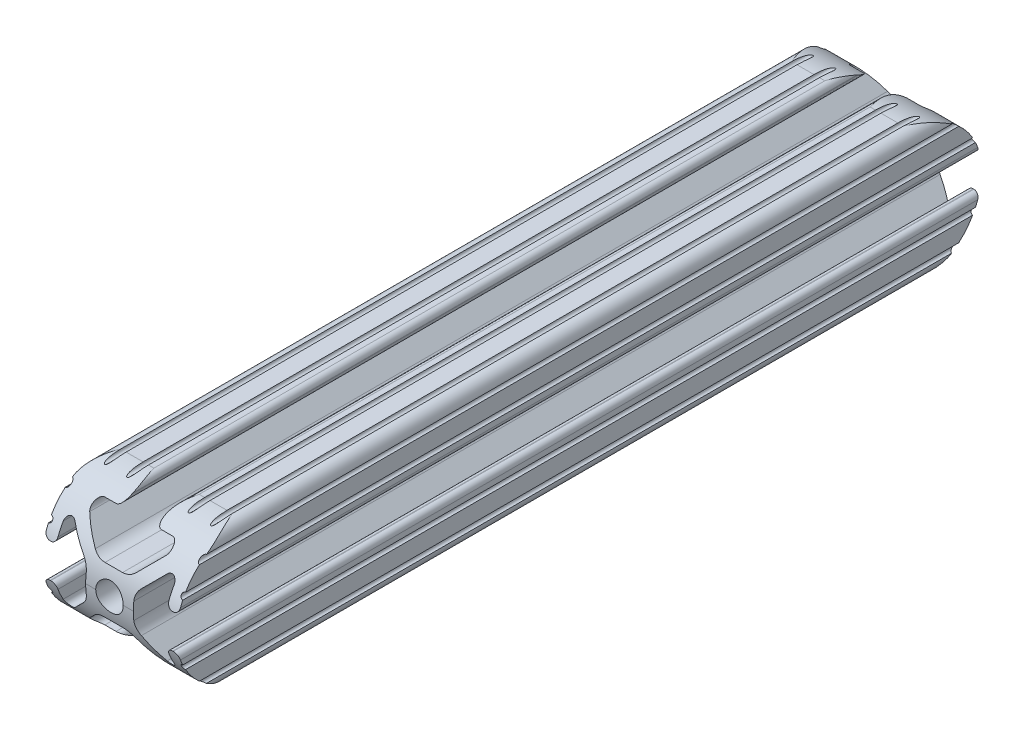
SolidWorks part; units mm, degrees
material "6061 Alloy"
ref_plane "Front Plane" through (0, 0, 0) normal (0, 0, 1) x (1, 0, 0)
ref_plane "Top Plane" through (0, 0, 0) normal (0, 1, 0) x (1, 0, 0)
ref_plane "Right Plane" through (0, 0, 0) normal (1, 0, 0) x (0, 0, -1)
sketch "Sketch1" plane through (0, 0, 0) normal (0, 0, 1) x (1, 0, 0)
  line L88 (-7.1797, -8.6452) -> (-3.9523, -5.4237)
  line L89 (-1.7093, -4.4958) -> (1.7093, -4.4958)
  line L90 (3.9523, -5.4237) -> (7.1797, -8.6452)
  line L91 (6.4164, -10.4902) -> (4.2875, -10.4902)
  line L92 (3.2385, -11.5392) -> (3.2385, -11.651)
  line L93 (4.2875, -12.7) -> (5.3171, -12.7)
  line L94 (6.3331, -12.7) -> (9.5504, -12.7)
  line L95 (12.7, -9.5504) -> (12.7, -6.3331)
  line L96 (12.7, -5.3171) -> (12.7, -4.2875)
  line L97 (11.651, -3.2385) -> (11.5392, -3.2385)
  line L98 (10.4902, -4.2875) -> (10.4902, -6.4021)
  line L99 (8.7371, -7.1294) -> (5.441, -3.8408)
  line L100 (4.5085, -1.5932) -> (4.5085, 1.5932)
  line L101 (5.441, 3.8408) -> (8.7371, 7.1294)
  line L102 (10.4902, 6.4021) -> (10.4902, 4.2875)
  line L103 (11.5392, 3.2385) -> (11.651, 3.2385)
  line L104 (12.7, 4.2875) -> (12.7, 5.3171)
  line L105 (12.7, 6.3331) -> (12.7, 9.5504)
  line L106 (9.5504, 12.7) -> (6.3331, 12.7)
  line L107 (5.3171, 12.7) -> (4.2875, 12.7)
  line L108 (3.2385, 11.651) -> (3.2385, 11.5392)
  line L109 (4.2875, 10.4902) -> (6.4768, 10.4902)
  line L110 (7.207, 8.7244) -> (3.8983, 5.4232)
  line L111 (1.6558, 4.4958) -> (-1.6558, 4.4958)
  line L112 (-3.8983, 5.4232) -> (-7.207, 8.7244)
  line L113 (-6.4768, 10.4902) -> (-4.2875, 10.4902)
  line L114 (-3.2385, 11.5392) -> (-3.2385, 11.651)
  line L115 (-4.2875, 12.7) -> (-5.3171, 12.7)
  line L116 (-6.3331, 12.7) -> (-9.5504, 12.7)
  line L117 (-12.7, 9.5504) -> (-12.7, 6.3331)
  line L118 (-12.7, 5.3171) -> (-12.7, 4.2875)
  line L119 (-11.651, 3.2385) -> (-11.5392, 3.2385)
  line L120 (-10.4902, 4.2875) -> (-10.4902, 6.4021)
  line L121 (-8.7371, 7.1294) -> (-5.441, 3.8408)
  line L122 (-4.5085, 1.5932) -> (-4.5085, -1.5932)
  line L123 (-5.441, -3.8408) -> (-8.7371, -7.1294)
  line L124 (-10.4902, -6.4021) -> (-10.4902, -4.2875)
  line L125 (-11.5392, -3.2385) -> (-11.651, -3.2385)
  line L126 (-12.7, -4.2875) -> (-12.7, -5.3171)
  line L127 (-12.7, -6.3331) -> (-12.7, -9.5504)
  line L128 (-9.5504, -12.7) -> (-6.3331, -12.7)
  line L129 (-5.3171, -12.7) -> (-4.2875, -12.7)
  line L130 (-3.2385, -11.651) -> (-3.2385, -11.5392)
  line L131 (-4.2875, -10.4902) -> (-6.4164, -10.4902)
  circle A1 centre (0, 0) radius 2.6035
  arc A104 (-7.1797, -8.6452) -> (-6.4164, -10.4902) centre (-6.4164, -9.4098) ccw
  arc A105 (-1.7093, -4.4958) -> (-3.9523, -5.4237) centre (-1.7093, -7.6708) ccw
  arc A106 (3.9523, -5.4237) -> (1.7093, -4.4958) centre (1.7093, -7.6708) ccw
  arc A107 (6.4164, -10.4902) -> (7.1797, -8.6452) centre (6.4164, -9.4098) ccw
  arc A108 (4.2875, -10.4902) -> (3.2385, -11.5392) centre (4.2875, -11.5392) ccw
  arc A109 (3.2385, -11.651) -> (4.2875, -12.7) centre (4.2875, -11.651) ccw
  arc A110 (6.3331, -12.7) -> (5.3171, -12.7) centre (5.8251, -12.7) ccw
  arc A111 (10.5664, -12.6998) -> (9.5504, -12.7) centre (10.0584, -12.7) ccw
  arc A112 (10.5664, -12.6998) -> (12.6998, -10.5664) centre (10.5918, -10.5918) ccw
  arc A113 (12.7, -9.5504) -> (12.6998, -10.5664) centre (12.7, -10.0584) ccw
  arc A114 (12.7, -5.3171) -> (12.7, -6.3331) centre (12.7, -5.8251) ccw
  arc A115 (12.7, -4.2875) -> (11.651, -3.2385) centre (11.651, -4.2875) ccw
  arc A116 (11.5392, -3.2385) -> (10.4902, -4.2875) centre (11.5392, -4.2875) ccw
  arc A117 (8.7371, -7.1294) -> (10.4902, -6.4021) centre (9.4628, -6.4021) ccw
  arc A118 (4.5085, -1.5932) -> (5.441, -3.8408) centre (7.6835, -1.5932) ccw
  arc A119 (5.441, 3.8408) -> (4.5085, 1.5932) centre (7.6835, 1.5932) ccw
  arc A120 (10.4902, 6.4021) -> (8.7371, 7.1294) centre (9.4628, 6.4021) ccw
  arc A121 (10.4902, 4.2875) -> (11.5392, 3.2385) centre (11.5392, 4.2875) ccw
  arc A122 (11.651, 3.2385) -> (12.7, 4.2875) centre (11.651, 4.2875) ccw
  arc A123 (12.7, 6.3331) -> (12.7, 5.3171) centre (12.7, 5.8251) ccw
  arc A124 (12.6998, 10.5664) -> (12.7, 9.5504) centre (12.7, 10.0584) ccw
  arc A125 (12.6998, 10.5664) -> (10.5664, 12.6998) centre (10.5918, 10.5918) ccw
  arc A126 (9.5504, 12.7) -> (10.5664, 12.6998) centre (10.0584, 12.7) ccw
  arc A127 (5.3171, 12.7) -> (6.3331, 12.7) centre (5.8251, 12.7) ccw
  arc A128 (4.2875, 12.7) -> (3.2385, 11.651) centre (4.2875, 11.651) ccw
  arc A129 (3.2385, 11.5392) -> (4.2875, 10.4902) centre (4.2875, 11.5392) ccw
  arc A130 (7.207, 8.7244) -> (6.4768, 10.4902) centre (6.4768, 9.4563) ccw
  arc A131 (1.6558, 4.4958) -> (3.8983, 5.4232) centre (1.6558, 7.6708) ccw
  arc A132 (-3.8983, 5.4232) -> (-1.6558, 4.4958) centre (-1.6558, 7.6708) ccw
  arc A133 (-6.4768, 10.4902) -> (-7.207, 8.7244) centre (-6.4768, 9.4563) ccw
  arc A134 (-4.2875, 10.4902) -> (-3.2385, 11.5392) centre (-4.2875, 11.5392) ccw
  arc A135 (-3.2385, 11.651) -> (-4.2875, 12.7) centre (-4.2875, 11.651) ccw
  arc A136 (-6.3331, 12.7) -> (-5.3171, 12.7) centre (-5.8251, 12.7) ccw
  arc A137 (-10.5664, 12.6998) -> (-9.5504, 12.7) centre (-10.0584, 12.7) ccw
  arc A138 (-10.5664, 12.6998) -> (-12.6998, 10.5664) centre (-10.5918, 10.5918) ccw
  arc A139 (-12.7, 9.5504) -> (-12.6998, 10.5664) centre (-12.7, 10.0584) ccw
  arc A140 (-12.7, 5.3171) -> (-12.7, 6.3331) centre (-12.7, 5.8251) ccw
  arc A141 (-12.7, 4.2875) -> (-11.651, 3.2385) centre (-11.651, 4.2875) ccw
  arc A142 (-11.5392, 3.2385) -> (-10.4902, 4.2875) centre (-11.5392, 4.2875) ccw
  arc A143 (-8.7371, 7.1294) -> (-10.4902, 6.4021) centre (-9.4628, 6.4021) ccw
  arc A144 (-4.5085, 1.5932) -> (-5.441, 3.8408) centre (-7.6835, 1.5932) ccw
  arc A145 (-5.441, -3.8408) -> (-4.5085, -1.5932) centre (-7.6835, -1.5932) ccw
  arc A146 (-10.4902, -6.4021) -> (-8.7371, -7.1294) centre (-9.4628, -6.4021) ccw
  arc A147 (-10.4902, -4.2875) -> (-11.5392, -3.2385) centre (-11.5392, -4.2875) ccw
  arc A148 (-11.651, -3.2385) -> (-12.7, -4.2875) centre (-11.651, -4.2875) ccw
  arc A149 (-12.7, -6.3331) -> (-12.7, -5.3171) centre (-12.7, -5.8251) ccw
  arc A150 (-12.6998, -10.5664) -> (-12.7, -9.5504) centre (-12.7, -10.0584) ccw
  arc A151 (-12.6998, -10.5664) -> (-10.5664, -12.6998) centre (-10.5918, -10.5918) ccw
  arc A152 (-9.5504, -12.7) -> (-10.5664, -12.6998) centre (-10.0584, -12.7) ccw
  arc A153 (-5.3171, -12.7) -> (-6.3331, -12.7) centre (-5.8251, -12.7) ccw
  arc A154 (-4.2875, -12.7) -> (-3.2385, -11.651) centre (-4.2875, -11.651) ccw
  arc A155 (-3.2385, -11.5392) -> (-4.2875, -10.4902) centre (-4.2875, -11.5392) ccw
extrude "Boss-Extrude1" add sketch "Sketch1" along normal mid plane 152.4
sketch "Sketch2" plane through (12.7, 0, 0) normal (1, 0, 0) x (0, 0, -1)
  line L0 (-76.2, 0) -> (76.2, 0) construction
  line L1 (-76.2, -1.5932) -> (-76.2, 1.5932) construction
  line L2 (76.2, -1.5932) -> (76.2, 1.5932) construction
  circle A0 centre (-63.5, 0) radius 3.175
  circle A1 centre (-38.1, 0) radius 3.175
  dimension "D1" = 12.7
  dimension "D3" = 6.35
  dimension "D2" = 25.4
fillet "Fillet1" radius 12.7 4 edges at (7.9418, -12.7, -76.2) (7.9418, 12.7, -76.2) (7.9418, -12.7, 76.2) (7.9418, 12.7, 76.2)
extrude "Cut-Extrude1" cut sketch "Sketch2" against normal through all
